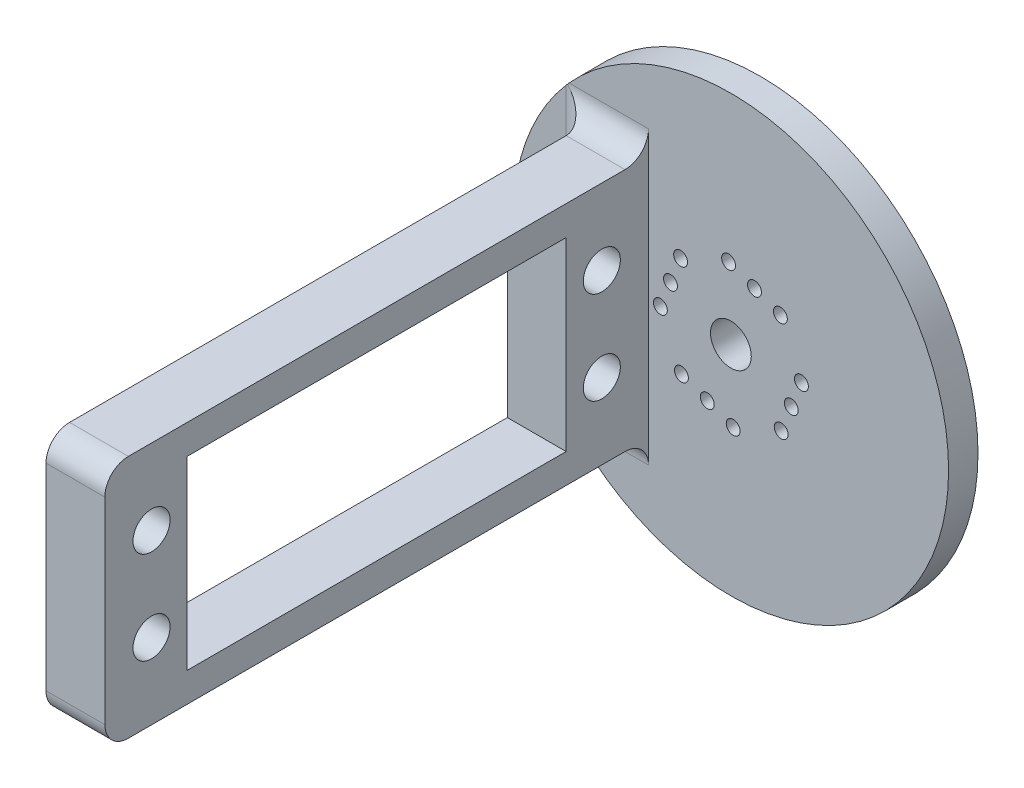
SolidWorks part; units mm, degrees
ref_plane "Front Plane" through (0, 0, 0) normal (0, 0, 1) x (1, 0, 0)
ref_plane "Top Plane" through (0, 0, 0) normal (0, 1, 0) x (1, 0, 0)
ref_plane "Right Plane" through (0, 0, 0) normal (1, 0, 0) x (0, 0, -1)
sketch "Sketch1" plane through (0, 0, 0) normal (0, 0, 1) x (1, 0, 0)
  circle A0 centre (0, 0) radius 23.495
  dimension "D1" = 46.99
extrude "Boss-Extrude1" add sketch "Sketch1" along normal blind 3.175
sketch "Sketch2" plane through (0, 0, 3.175) normal (0, 0, 1) x (1, 0, 0)
  line L1 (-12.065, 15.875) -> (-8.89, 15.875)
  line L2 (-12.065, 15.875) -> (-12.065, -15.875)
  line L3 (-12.065, -15.875) -> (-8.89, -15.875)
  line L4 (-8.89, 15.875) -> (-8.89, -15.875)
  point P4 (-8.89, 0)
  dimension "D1" = 3.175
  dimension "D2" = 8.89
  dimension "D3" = 31.75
ref_plane "Plane4" through (-8.89, 0, 0) normal (1, 0, 0) x (0, 0, -1)
sketch "Sketch4" plane through (-8.89, 0, 0) normal (1, 0, 0) x (0, 0, -1)
  line L0 (-3.175, 15.875) -> (-3.175, -15.875) construction
  line L2 (-3.175, 13.175) -> (-61.855, 13.175)
  line L3 (-3.175, 13.175) -> (-3.175, -13.175)
  line L4 (-3.175, -13.175) -> (-61.855, -13.175)
  line L5 (-61.855, 13.175) -> (-61.855, -13.175)
  point P0 (-12.065, 0)
  point P9 (-52.965, 0)
  point P10 (-61.855, 0)
  line B0 (-12.065, -10) -> (-12.065, 10)
  line B1 (-12.065, -10) -> (-52.965, -10)
  line B2 (-52.965, -10) -> (-52.965, 10)
  line B3 (-12.065, 10) -> (-52.965, 10)
  circle B4 centre (-56.815, -5) radius 2
  circle B5 centre (-56.815, 5) radius 2
  circle B6 centre (-8.215, -5) radius 2
  circle B7 centre (-8.215, 5) radius 2
  dimension "D1" = 8.89
  dimension "D2" = 8.89
  dimension "D3" = 3.175
sketch_block_instance "Block1-2"
sketch_block "Block1" parameters "D1"=4, "D2"=10, "D3"=48.6, "D4"=40.9, "D5"=20
extrude "Boss-Extrude3" add sketch "Sketch4" against normal blind 6.35
fillet "Fillet1" radius 2.54 3 edges at (-12.065, 13.175, 3.175) (-12.065, -13.175, 3.175) (-15.24, 0, 3.175)
sketch "Sketch5" plane through (0, 0, 0) normal (0, 0, -1) x (-1, 0, 0)
  circle B0 centre (0, 0) radius 1.5
  circle B1 centre (-7.6118, 0.2465) radius 0.75
  circle B2 centre (-6.5199, -2.5478) radius 0.75
  circle B3 centre (-5.428, -5.342) radius 0.75
  circle B4 centre (-0.2465, -7.6118) radius 0.75
  circle B5 centre (2.5478, -6.5199) radius 0.75
  circle B6 centre (5.342, -5.428) radius 0.75
  circle B7 centre (7.6118, -0.2465) radius 0.75
  circle B8 centre (6.5199, 2.5478) radius 0.75
  circle B9 centre (5.428, 5.342) radius 0.75
  circle B10 centre (0.2465, 7.6118) radius 0.75
  circle B11 centre (-2.5478, 6.5199) radius 0.75
  circle B12 centre (-5.342, 5.428) radius 0.75
  circle B13 centre (0, 0) radius 10
sketch_block_instance "ServoHornBlock-1"
sketch_block "ServoHornBlock"
extrude "Cut-Extrude1" cut sketch "Sketch5" against normal up to next contours B6 | B5 | B4 | B3 | B2 | B1 | B12 | B11 | B10 | B9 | B8 | B7 | B0 region at (0, 0, 0) region at (7.6118, 0.2465, 0) region at (6.5199, -2.5478, 0) region at (5.428, -5.342, 0) region at (0.2465, -7.6118, 0) region at (-2.5478, -6.5199, 0) region at (-5.342, -5.428, 0) region at (-7.6118, -0.2465, 0) region at (-6.5199, 2.5478, 0) region at (-5.428, 5.342, 0) region at (-0.2465, 7.6118, 0) region at (2.5478, 6.5199, 0) region at (5.342, 5.428, 0)
sketch "Sketch6" plane through (0, 0, 3.175) normal (0, 0, 1) x (1, 0, 0)
  circle A0 centre (0, 0) radius 2.2
  dimension "D1" = 4.4
extrude "Cut-Extrude2" cut sketch "Sketch6" against normal through all
fillet "Fillet2" radius 2.54 2 edges at (-12.065, 13.175, 61.855) (-12.065, -13.175, 61.855)
